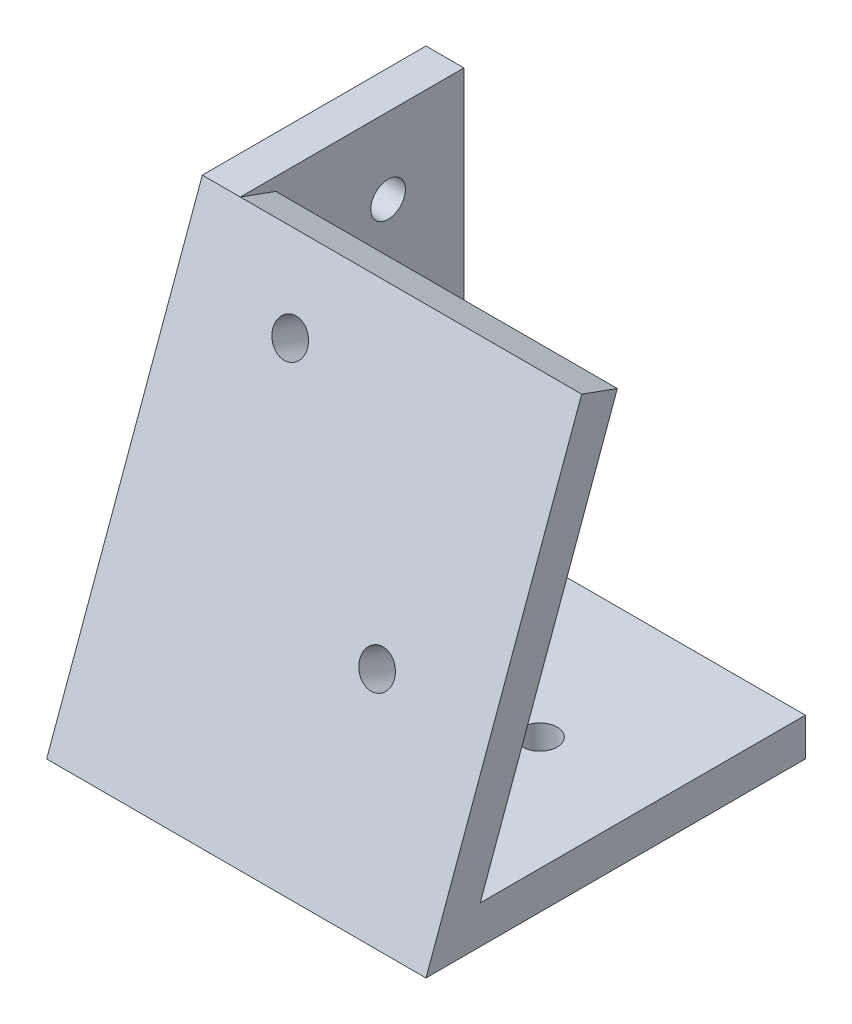
SolidWorks part; units mm, degrees
material "ABS"
ref_plane "Front Plane" through (0, 0, 0) normal (0, 0, 1) x (1, 0, 0)
ref_plane "Top Plane" through (0, 0, 0) normal (0, 1, 0) x (1, 0, 0)
ref_plane "Right Plane" through (0, 0, 0) normal (1, 0, 0) x (0, 0, -1)
sketch "Sketch1" plane through (0, 0, 0) normal (1, 0, 0) x (0, 0, -1)
  line L0 (0, 0) -> (-50, 0)
  line L1 (-50, 0) -> (-29.4788, 56.3816)
  line L2 (-29.4788, 56.3816) -> (-24.7803, 54.6715)
  line L3 (-24.7803, 54.6715) -> (-42.8593, 5)
  line L4 (-42.8593, 5) -> (0, 5)
  line L5 (0, 5) -> (0, 0)
  dimension "D1" = 60
  dimension "D2" = 50
  dimension "D3" = 70
  dimension "D4" = 5
  dimension "D5" = 5
extrude "Main" add sketch "Sketch1" along normal mid plane 50
sketch "Sketch2" plane through (0, 0, 0) normal (0, 0, -1) x (-1, 0, 0)
  line L0 (-25, 56.3816) -> (25, 56.3816) construction
  line L1 (-25, 0) -> (-20, 0)
  line L2 (-25, 0) -> (-25, 56.3816)
  line L3 (-25, 56.3816) -> (-20, 56.3816)
  line L4 (-20, 0) -> (-20, 56.3816)
  dimension "D1" = 5
extrude "Back" add sketch "Sketch2" against normal up to next
hole_wizard "Base Holes" positions "3DSketch4" profile "Sketch5" hole size "#8" standard "ANSI Inch"
sketch3d "3DSketch4"
  line L0 (-25, 5, 0) -> (-25, 5, 42.8593) construction
  line L3 (20, 5, 0) -> (-25, 5, 0) construction
  point P0 (10, 5, 20)
  point P2 (-10, 5, 20)
  dimension "D1" = 15
  dimension "D2" = 15
  dimension "D3" = 20
  dimension "D4" = 20
sketch "Sketch5" plane through (10, 5, 20) normal (1, 0, 0) x (0, 0, 1)
  line L0 (0, 0) -> (0, 5)
  line L1 (0, 5) -> (2.286, 5)
  line L2 (2.286, 5) -> (2.286, 0)
  line L5 (2.286, 0) -> (0, 0)
  line L10 (0, 5) -> (-2.286, 5) construction
  line L11 (0, -6.35) -> (0, 107.95) construction
  dimension "Hole Dia." = 4.572
  dimension "Hole Depth" = 5
  dimension "Drill Angle" = 180
hole_wizard "BackPanelHoles" positions "Sketch6" profile "Sketch7" hole size "#8" standard "ANSI Inch"
sketch "Sketch6" plane through (20, 0, 0) normal (-1, 0, 0) x (0, 0, 1)
  line L0 (29.4788, 56.3816) -> (0, 56.3816) construction
  line L1 (0, 5) -> (0, 56.3816) construction
  line L2 (50, 0) -> (0, 0) construction
  point P0 (10, 46.3816)
  point P2 (25, 20)
  dimension "D1" = 10
  dimension "D2" = 10
  dimension "D3" = 20
  dimension "D4" = 25
sketch "Sketch7" plane through (20, 46.3816, 10) normal (0, 1, 0) x (0, 0, 1)
  line L0 (0, 0) -> (0, 5)
  line L1 (0, 5) -> (2.286, 5)
  line L2 (2.286, 5) -> (2.286, 0)
  line L5 (2.286, 0) -> (0, 0)
  line L10 (0, 5) -> (-2.286, 5) construction
  line L11 (0, -6.35) -> (0, 107.95) construction
  dimension "Hole Dia." = 4.572
  dimension "Hole Depth" = 5
  dimension "Drill Angle" = 180
hole_wizard "#8 (0.18) Diameter Hole3" positions "3DSketch5" profile "Sketch8" hole size "#8" standard "ANSI Inch"
sketch3d "3DSketch5"
  line L1 (20, 56.3816, 29.4788) -> (-25, 56.3816, 29.4788) construction
  line L2 (25, 0, 50) -> (-25, 0, 50) construction
  line L3 (-25, 56.3816, 29.4788) -> (-25, 0, 50) construction
  line L4 (25, 56.3816, 29.4788) -> (25, 0, 50) construction
  point P0 (-10, 46.9846, 32.899)
  point P2 (10, 23.4923, 41.4495)
  dimension "D1" = 15
  dimension "D2" = 10
  dimension "D3" = 25
  dimension "D4" = 15
sketch "Sketch8" plane through (-10, 46.9846, 32.899) normal (1, 0, 0) x (0, -0.9397, 0.342)
  line L0 (0, 0) -> (0, 5)
  line L1 (0, 5) -> (2.286, 5)
  line L2 (2.286, 5) -> (2.286, 0)
  line L5 (2.286, 0) -> (0, 0)
  line L10 (0, 5) -> (-2.286, 5) construction
  line L11 (0, -6.35) -> (0, 107.95) construction
  dimension "Hole Dia." = 4.572
  dimension "Hole Depth" = 5
  dimension "Drill Angle" = 180
ref_plane "Midplane" through (0, 0, 0) normal (-1, 0, 0) x (0, 0, 1)
mirror "Mirror1" about plane through (0, 0, 0) normal (-1, 0, 0) of "BackPanelHoles", "Back"
sketch "Sketch9" plane through (20, 0, 0) normal (-1, 0, 0) x (0, 0, 1)
  line L0 (29.4788, 56.3816) -> (0, 56.3816)
  line L1 (0, 56.3816) -> (0, 5)
  line L2 (0, 5) -> (42.8593, 5)
  line L3 (42.8593, 5) -> (24.7803, 54.6715)
  line L4 (24.7803, 54.6715) -> (29.4788, 56.3816)
extrude "Cut-Extrude1" cut sketch "Sketch9" against normal up to next
